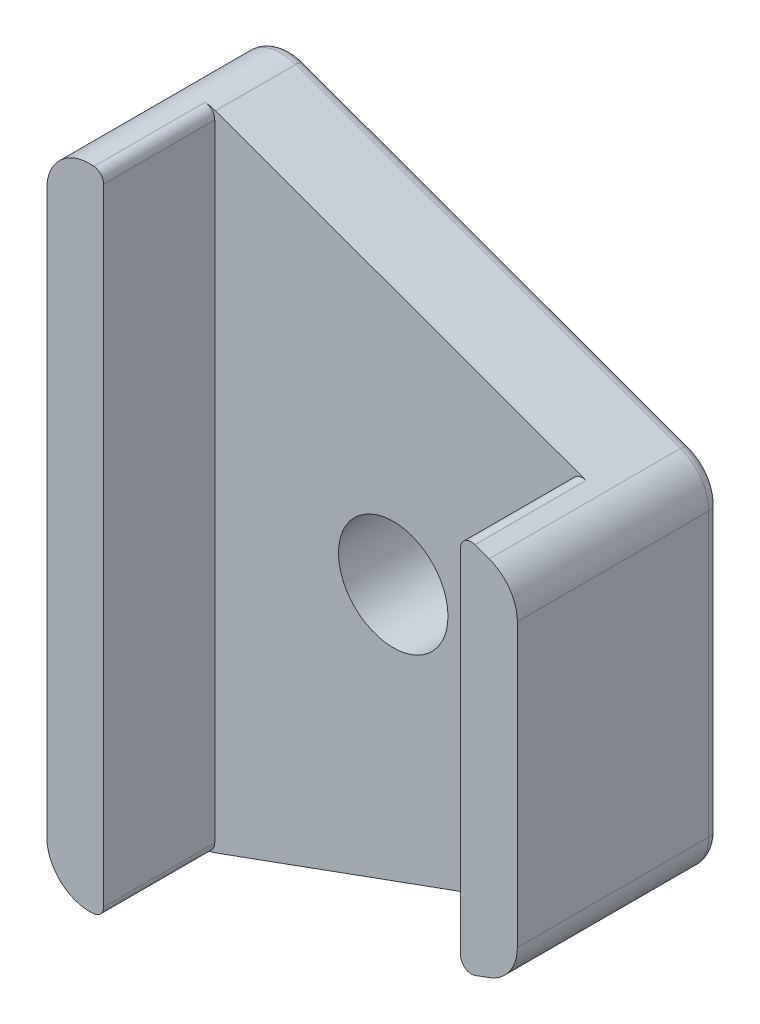
SolidWorks part; units mm, degrees
ref_plane "Front Plane" through (0, 0, 0) normal (0, 0, 1) x (1, 0, 0)
ref_plane "Top Plane" through (0, 0, 0) normal (0, 1, 0) x (1, 0, 0)
ref_plane "Right Plane" through (0, 0, 0) normal (1, 0, 0) x (0, 0, -1)
sketch "Sketch1" plane through (0, 0, 0) normal (0, 0, 1) x (1, 0, 0)
  line L0 (-11.6417, 0) -> (-2.9104, 0) construction
  line L1 (5.8208, -6.35) -> (-11.6417, -12.7)
  line L2 (5.8208, -6.35) -> (5.8208, 6.35)
  line L3 (5.8208, 6.35) -> (-11.6417, 12.7)
  line L4 (-11.6417, -12.7) -> (-11.6417, 12.7)
  line L5 (5.8208, -6.35) -> (-11.6417, 12.7) construction
  line L6 (5.8208, 6.35) -> (-11.6417, -12.7) construction
  line L7 (-2.9104, 0) -> (5.8208, 0) construction
  circle A0 centre (-2.9104, 0) radius 2.032
  point P0 (0, 0)
  dimension "D2" = 4.064
  dimension "D1" = 17.4625
  dimension "D3" = 12.7
  dimension "D4" = 25.4
extrude "Boss-Extrude1" add sketch "Sketch1" along normal blind 3.375
sketch "Sketch2" plane through (0, 0, 3.375) normal (0, 0, 1) x (1, 0, 0)
  line L0 (-11.6417, -12.7) -> (5.8208, -6.35) construction
  line L2 (-11.6417, 12.7) -> (-11.6417, -12.7)
  line L4 (-9.5354, 11.9341) -> (-9.5354, -11.9341)
  line L5 (5.8208, 6.35) -> (-11.6417, 12.7) construction
  line L7 (5.8208, 6.35) -> (5.8208, -6.35)
  line L9 (3.7146, 7.1159) -> (3.7146, -7.1159)
  line L10 (-11.6417, -12.7) -> (-9.5354, -11.9341)
  line L11 (5.8208, 6.35) -> (3.7146, 7.1159)
  line L12 (3.7146, -7.1159) -> (5.8208, -6.35)
  line L13 (-9.5354, 11.9341) -> (-11.6417, 12.7)
  circle A0 centre (-2.9104, 0) radius 6.625 construction
  point P12 (-10.8447, -12.7)
  point P16 (-8.9823, -11.973)
  point P17 (-8.8382, 11.9167)
  point P20 (-2.7112, 0)
  point P22 (5.4223, -6.35)
  point P24 (3.9138, 6.9389)
  dimension "D2" = 13.25
extrude "Boss-Extrude2" add sketch "Sketch2" along normal blind 4.125
fillet "Fillet1" radius 1.5875 4 edges at (5.8208, -6.35, 3.75) (-11.6417, -12.7, 3.75) (-11.6417, 12.7, 3.75) (5.8208, 6.35, 3.75)
fillet "Fillet2" radius 0.3969 12 edges at (3.7146, -7.1159, 5.4375) (-9.5354, -11.9339, 5.4375) (3.7146, 7.1159, 5.4375) (-9.5354, 11.9339, 5.4375) (5.5336, 6.1488, 0) (5.8208, 0, 0) (5.5336, -6.1488, 0) (-2.3679, -9.3277, 0) (-10.9649, -11.7338, 0) (-11.6417, 0, 0) (-10.9649, 11.7338, 0) (-2.3679, 9.3277, 0)
